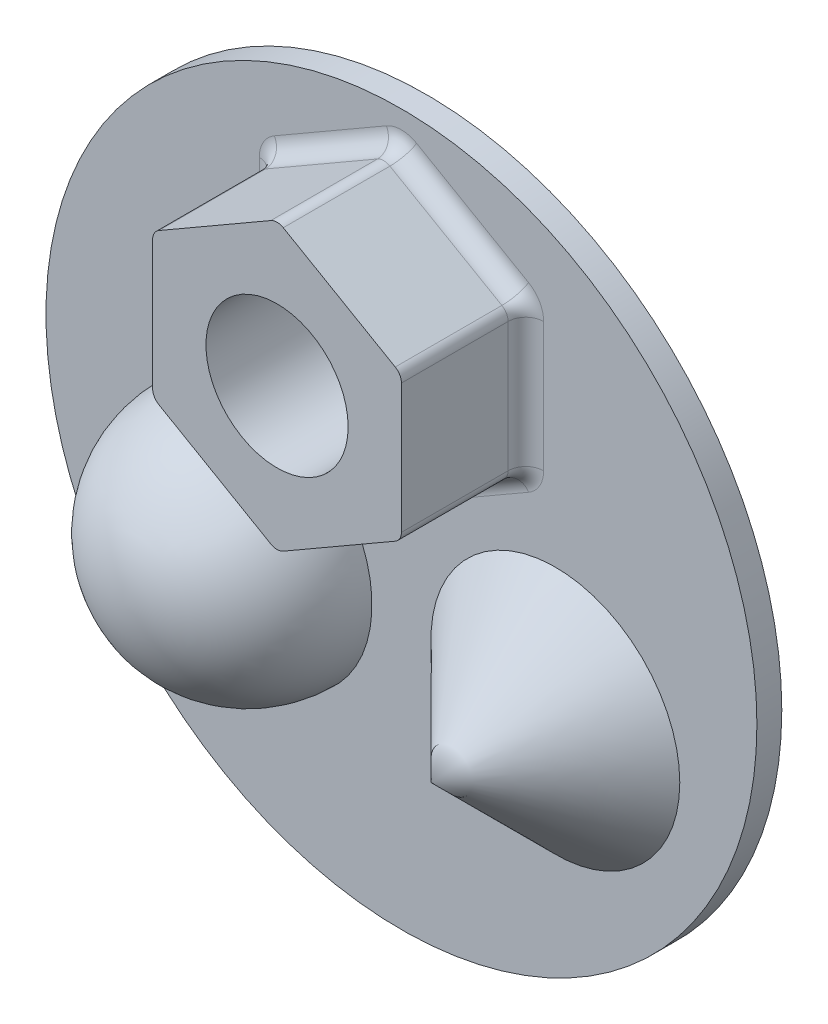
SolidWorks part; units mm, degrees
ref_plane "Front Plane" through (0, 0, 0) normal (0, 0, 1) x (1, 0, 0)
ref_plane "Top Plane" through (0, 0, 0) normal (0, 1, 0) x (1, 0, 0)
ref_plane "Right Plane" through (0, 0, 0) normal (1, 0, 0) x (0, 0, -1)
sketch "Sketch1" plane through (0, 0, 0) normal (0, 0, 1) x (1, 0, 0)
  circle A0 centre (0, 0) radius 10
  dimension "D1" = 20
extrude "Boss-Extrude1" add sketch "Sketch1" along normal blind 0.7
sketch "Sketch2" plane through (0, 0, 0.7) normal (0, 0, 1) x (1, 0, 0)
  line L0 (0, 5) -> (0, 0) construction
  line L1 (0, 0.9585) -> (3.5, 2.9793)
  line L2 (3.5, 2.9793) -> (3.5, 7.0207)
  line L3 (3.5, 7.0207) -> (0, 9.0415)
  line L4 (0, 9.0415) -> (-3.5, 7.0207)
  line L5 (-3.5, 7.0207) -> (-3.5, 2.9793)
  line L6 (-3.5, 2.9793) -> (0, 0.9585)
  line L7 (0, 0) -> (-4.3301, -2.5) construction
  line L8 (0, 0) -> (4.3301, -2.5) construction
  line L9 (-4.3301, -6) -> (-4.3301, 1)
  circle A0 centre (0, 5) radius 3.5 construction
  circle A1 centre (0, 0) radius 5 construction
  circle A3 centre (4.3301, -2.5) radius 3.5
  arc A4 (-4.3301, 1) -> (-4.3301, -6) centre (-4.3301, -2.5) ccw
  dimension "D1" = 10
  dimension "D2" = 7
  dimension "D5" = 3.5
  dimension "D3" = 120
  dimension "D4" = 120
revolve "Revolve1" add sketch "Sketch2" angle 180 about L9 region at (-5.8156, -2.5, 0.7)
extrude "Boss-Extrude2" add sketch "Sketch2<5>" along normal blind 5 draft 45 contours A3
sketch "Sketch2<5>" plane through (0, 0, 0.7) normal (0, 0, 1) x (1, 0, 0) same geometry as "Sketch2"
extrude "Boss-Extrude3" add sketch "Sketch2<6>" along normal up to vertex (3.5 mm away) contours L6 L1 L2 L3 L4 L5 up to point (4.3301, -2.5, 4.2)
sketch "Sketch2<6>" plane through (0, 0, 0.7) normal (0, 0, 1) x (1, 0, 0) same geometry as "Sketch2"
fillet "Fillet1" radius 0.35 6 edges at (0, 9.0415, 2.45) (-3.5, 7.0207, 2.45) (-3.5, 2.9793, 2.45) (3.5, 7.0207, 2.45) (3.5, 2.9793, 2.45) (0, 0.9585, 2.45)
sketch "Sketch3" plane through (0, 0, 4.2) normal (0, 0, 1) x (1, 0, 0)
  line L0 (0.175, 1.0596) -> (3.325, 2.8782) construction
  line L1 (-3.5, 6.8187) -> (-3.5, 3.1813) construction
  line L2 (3.325, 7.1218) -> (0.175, 8.9404) construction
  circle A0 centre (0, 5) radius 2
  circle A1 centre (0, 5) radius 3.5 construction
  dimension "D1" = 4
extrude "Cut-Extrude1" cut sketch "Sketch3" against normal blind 10
fillet "Fillet2" radius 0.5 12 edges at (3.4531, 3.0063, 0.7) (1.75, 1.9689, 0.7) (0, 1.0127, 0.7) (-1.75, 1.9689, 0.7) (-3.4531, 3.0063, 0.7) (-3.5, 5, 0.7) (-3.4531, 6.9937, 0.7) (-1.75, 8.0311, 0.7) (0, 8.9873, 0.7) (1.75, 8.0311, 0.7) (3.4531, 6.9937, 0.7) (3.5, 5, 0.7)
sketch "Sketch4" plane through (0, 0, 0) normal (0, 0, -1) x (-1, 0, 0)
  circle A0 centre (-4.3301, -2.5) radius 2
  circle A1 centre (-4.3301, -2.5) radius 3.5 construction
  dimension "D1" = 1.5
extrude "Cut-Extrude2" cut sketch "Sketch4" against normal blind 10 draft 45
